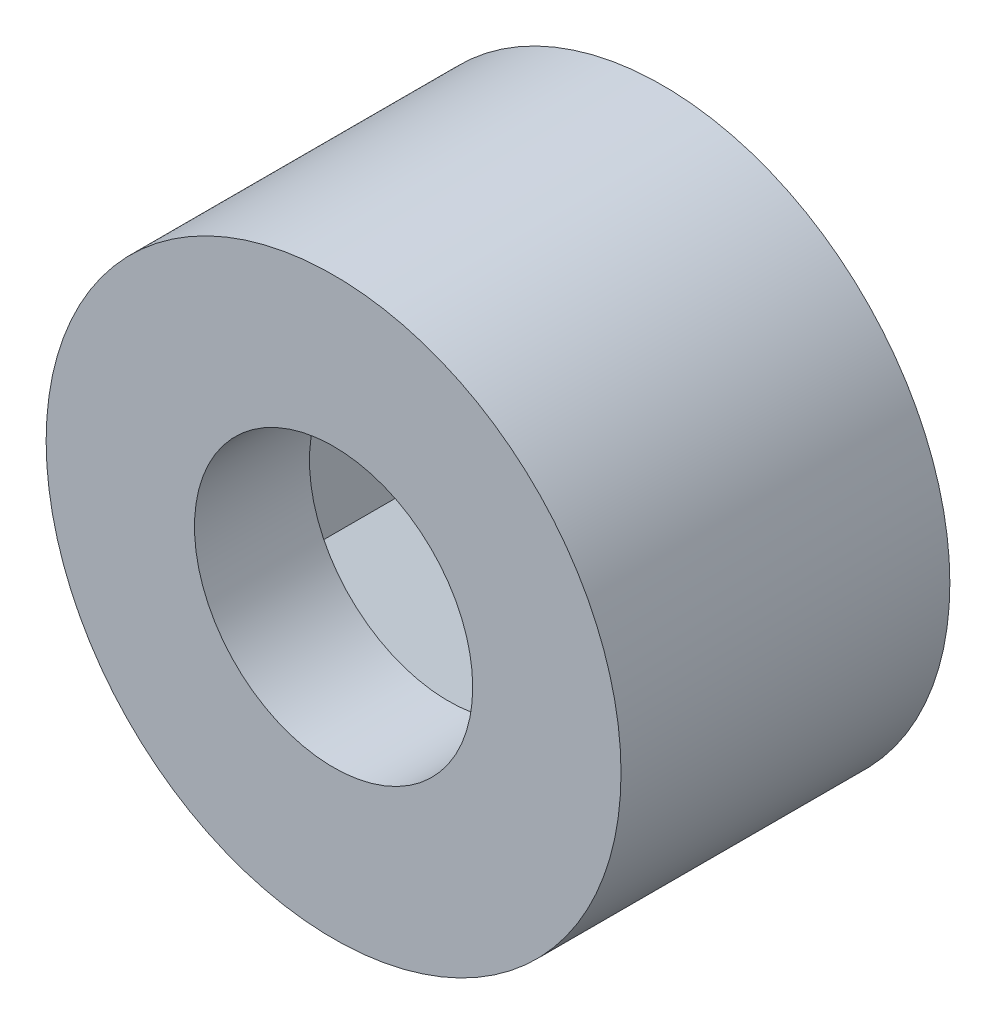
SolidWorks part; units mm, degrees
ref_plane "Front Plane" through (0, 0, 0) normal (0, 0, 1) x (1, 0, 0)
ref_plane "Top Plane" through (0, 0, 0) normal (0, 1, 0) x (1, 0, 0)
ref_plane "Right Plane" through (0, 0, 0) normal (1, 0, 0) x (0, 0, -1)
sketch "Sketch1" plane through (0, 0, 0) normal (0, 0, 1) x (1, 0, 0)
  line L1 (0, -7.5056) -> (6.5, -3.7528)
  line L2 (6.5, -3.7528) -> (6.5, 3.7528)
  line L3 (6.5, 3.7528) -> (0, 7.5056)
  line L4 (0, 7.5056) -> (-6.5, 3.7528)
  line L5 (-6.5, 3.7528) -> (-6.5, -3.7528)
  line L6 (-6.5, -3.7528) -> (0, -7.5056)
  circle A0 centre (0, 0) radius 6.5 construction
  circle A1 centre (0, 0) radius 12.5
  dimension "D1" = 13
  dimension "D2" = 25
extrude "Boss-Extrude1" add sketch "Sketch1" along normal blind 6.3
sketch "Sketch2" plane through (0, 0, 6.3) normal (0, 0, 1) x (1, 0, 0)
  circle A0 centre (0, 0) radius 6.05
  circle A2 centre (0, 0) radius 12.5 construction
  circle A3 centre (0, 0) radius 12.5
  dimension "D1" = 12.1
extrude "Boss-Extrude2" add sketch "Sketch2" along normal blind 5 contours A3 | A0
sketch "Sketch3" plane through (0, 0, 0) normal (0, 0, -1) x (-1, 0, 0)
  circle A0 centre (0, 0) radius 4
  circle A1 centre (0, 0) radius 12.5 construction
  circle A2 centre (0, 0) radius 12.5
  dimension "D1" = 8
extrude "Boss-Extrude3" add sketch "Sketch3" along normal blind 3
sketch "Sketch4" plane through (0, 0, 0) normal (0, 0, 1) x (1, 0, 0)
  circle A0 centre (0, 0) radius 4 construction
  circle A1 centre (0, 0) radius 4
extrude "Boss-Extrude4" add sketch "Sketch4" against normal blind 0.6
